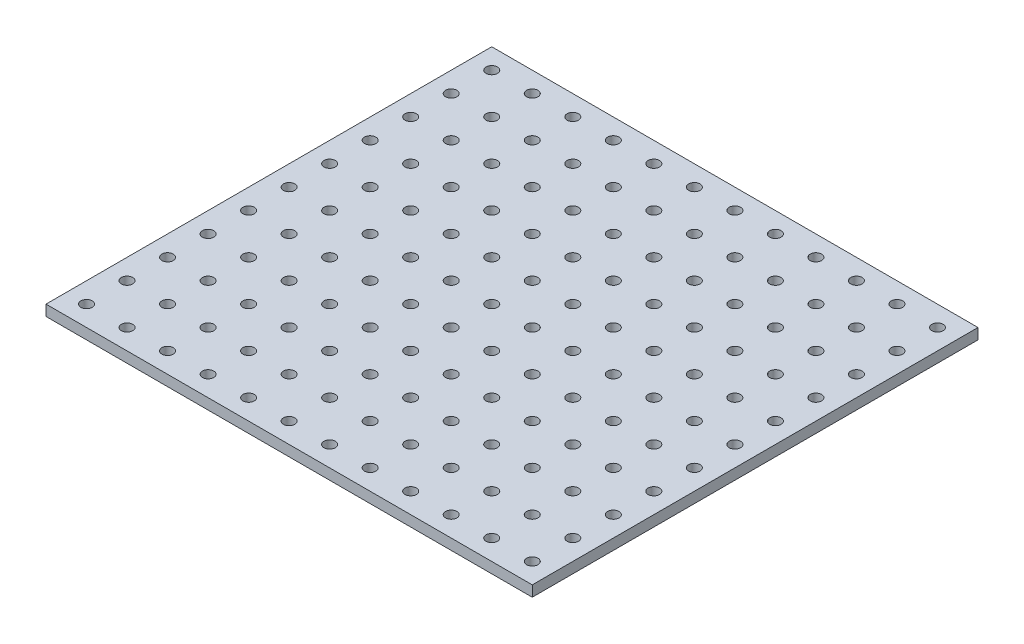
SolidWorks part; units mm, degrees
ref_plane "Front Plane" through (0, 0, 0) normal (0, 0, 1) x (1, 0, 0)
ref_plane "Top Plane" through (0, 0, 0) normal (0, 1, 0) x (1, 0, 0)
ref_plane "Right Plane" through (0, 0, 0) normal (1, 0, 0) x (0, 0, -1)
sketch "Sketch1" plane through (0, 0, 0) normal (0, 1, 0) x (1, 0, 0)
  line L0 (0, 20) -> (20, 0) construction
  line L1 (0, 0) -> (20, 0)
  line L2 (0, 0) -> (0, 20)
  line L3 (0, 20) -> (20, 20)
  line L4 (20, 0) -> (20, 20)
  circle A0 centre (10, 10) radius 2.8
  point P5 (10, 10)
  dimension "D3" = 5.6
  dimension "D1" = 20
  dimension "D2" = 20
extrude "Main Square" add sketch "Sketch1" along normal blind 5.5 contours L3 L0 A0 L4 | L0 L2 L1 A0 region at (13.4969, 0, -13.4969) region at (6.5031, 0, -6.5031)
sketch "Sketch2" plane through (0, 0, 0) normal (0, 0, 1) x (1, 0, 0)
  line L0 (10, 5.5) -> (10, 0) construction
  line L1 (0, 0) -> (20, 0) construction
  line L3 (0, 0.2) -> (0.2, 0.2)
  line L4 (0, 5.5) -> (0, 0) construction
  line L5 (0.2, 0.2) -> (0.2, 0)
  line L6 (0.2, 0) -> (0, 0)
  line L7 (0, 0) -> (0, 0.2)
  line L8 (20, 0) -> (20, 0.2)
  line L9 (19.8, 0) -> (20, 0)
  line L10 (19.8, 0.2) -> (19.8, 0)
  line L11 (20, 0.2) -> (19.8, 0.2)
  dimension "D1" = 0.2
  dimension "D2" = 0.2
extrude "AntiWarpCuts1" cut sketch "Sketch2" against normal through all both and the other way through all
sketch "Sketch3" plane through (0, 0, 0) normal (-1, 0, 0) x (0, 0, 1)
  line L0 (-10, 5.5) -> (-10, 0) construction
  line L3 (-0.2, 0) -> (-0.2, 0.2)
  line L4 (-20, 0) -> (-19.8, 0)
  line L5 (-20, 0) -> (-20, 0.2)
  line L6 (-20, 0.2) -> (-19.8, 0.2)
  line L7 (-19.8, 0) -> (-19.8, 0.2)
  line L8 (0, 0.2) -> (-0.2, 0.2)
  line L9 (0, 0) -> (0, 0.2)
  line L10 (0, 0) -> (-0.2, 0)
  dimension "D1" = 0.2
  dimension "D2" = 0.2
extrude "AntiWarpCuts2" cut sketch "Sketch3" against normal through all both and the other way through all
pattern_linear "LPattern2" count 12 spacing 20 along (1, 0, 0) count 11 spacing 20 along (0, 0, 1) of "AntiWarpCuts1", "AntiWarpCuts2", "Main Square"
